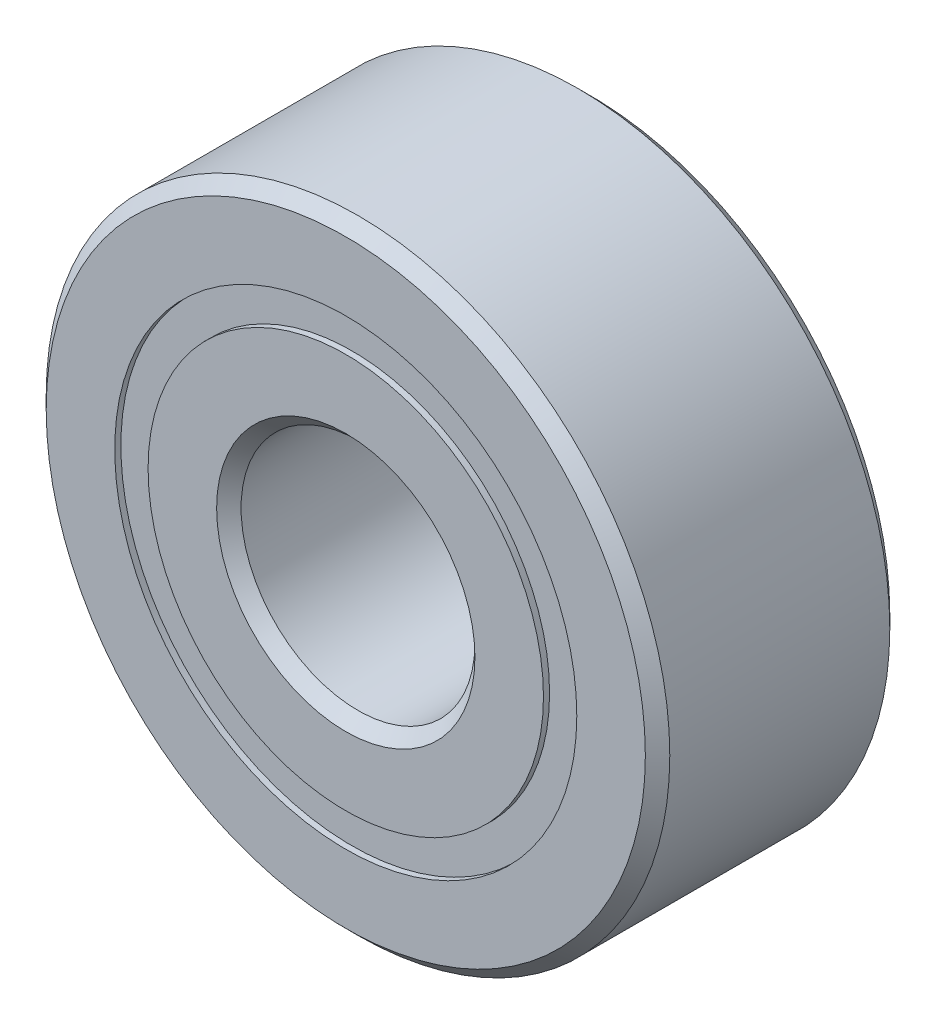
SolidWorks part; units mm, degrees
ref_plane "Front Plane" through (0, 0, 0) normal (0, 0, 1) x (1, 0, 0)
ref_plane "Top Plane" through (0, 0, 0) normal (0, 1, 0) x (1, 0, 0)
ref_plane "Right Plane" through (0, 0, 0) normal (1, 0, 0) x (0, 0, -1)
sketch "Sketch1" plane through (0, 0, 0) normal (1, 0, 0) x (0, 0, -1)
  line L0 (-2.4892, 0) -> (2.4892, 0) construction
  line L1 (0, 6.35) -> (0, -6.35) construction
  line L2 (2.2403, 6.35) -> (-2.2403, 6.35)
  line L3 (-2.2403, 6.35) -> (-2.4892, 6.1011)
  line L4 (-2.4892, 6.1011) -> (-2.4892, 4.705)
  line L5 (-2.4892, 4.705) -> (-1.1063, 4.705)
  line L6 (2.4892, 4.705) -> (1.1063, 4.705)
  line L7 (2.4892, 6.1011) -> (2.4892, 4.705)
  line L8 (2.2403, 6.35) -> (2.4892, 6.1011)
  line L9 (0, 6.35) -> (0, 4.3656) construction
  line L10 (0, 4.3656) -> (0, 2.3813) construction
  arc A0 (-1.1063, 4.705) -> (1.1063, 4.705) centre (0, 4.3656) cw
  point P14 (0, 2.3813)
  dimension "Width" = 4.9784
  dimension "OD" = 12.7
  dimension "D1" = 45
  dimension "D2" = 0.2489
  dimension "D3" = 2.2126
  dimension "D4" = 0.3394
revolve "Revolve1" add sketch "Sketch1" angle 360 about L0
sketch "Sketch3" plane through (0, 0, 0) normal (1, 0, 0) x (0, 0, -1)
  line L0 (-1.1063, 4.0262) -> (-2.4892, 4.0262)
  line L1 (-2.4892, 6.1011) -> (-2.4892, 4.705) construction
  line L2 (-2.2403, 6.35) -> (-2.4892, 6.1011) construction
  line L3 (-2.4892, 4.0262) -> (-2.4892, 2.6302)
  line L5 (-2.4892, 2.6302) -> (-2.2403, 2.3813)
  line L6 (-2.2403, 2.3813) -> (2.2403, 2.3812)
  line L7 (2.2403, 6.35) -> (2.2403, -6.35) construction
  line L8 (2.2403, 2.3812) -> (2.4892, 2.6302)
  line L9 (2.4892, -6.1011) -> (2.4892, 6.1011) construction
  line L10 (2.4892, 2.6302) -> (2.4892, 4.0262)
  line L11 (2.4892, 4.0262) -> (1.1063, 4.0262)
  line L12 (0, 6.35) -> (0, -6.35) construction
  line L13 (2.2403, 6.35) -> (2.4892, 6.1011) construction
  arc A1 (1.1063, 4.0262) -> (-1.1063, 4.0262) centre (0, 4.3656) cw
  arc A2 (1.1063, 4.705) -> (-1.1063, 4.705) centre (0, 4.3656) ccw construction
revolve "Revolve3" add sketch "Sketch3" angle 360 about L0
sketch "Sketch4" plane through (0, 0, 0) normal (1, 0, 0) x (0, 0, -1)
  line L0 (-1.1572, 4.3656) -> (1.1572, 4.3656)
  arc A2 (-1.1572, 4.3656) -> (1.1572, 4.3656) centre (0, 4.3656) cw
  arc A3 (1.1063, 4.705) -> (-1.1063, 4.705) centre (0, 4.3656) ccw construction
revolve "Revolve4" add sketch "Sketch4" angle 360 about L0
ref_axis "Axis1" through (0, 0, -2.4892) along (0, 0, 1)
pattern_circular "CirPattern1" count 10 every 36 about axis through (0, 0, -2.4892) along (0, 0, 1) of bodies 104
sketch "Sketch5" plane through (0, 0, 0) normal (1, 0, 0) x (0, 0, -1)
  line L0 (-2.4892, 4.705) -> (-1.1063, 4.705) construction
  line L1 (-2.3647, 4.705) -> (-1.1572, 4.705)
  line L2 (-2.3647, 4.705) -> (-2.3647, 4.0262)
  line L3 (-2.3647, 4.0262) -> (-1.1572, 4.0262)
  line L4 (-1.1572, 4.705) -> (-1.1572, 4.0262)
  line L5 (-1.1063, 4.0262) -> (-2.4892, 4.0262) construction
  line L6 (2.4892, 4.705) -> (1.1063, 4.705) construction
  line L7 (2.3647, 4.705) -> (1.1572, 4.705)
  line L8 (2.3647, 4.705) -> (2.3647, 4.0262)
  line L9 (2.3647, 4.0262) -> (1.1572, 4.0262)
  line L10 (1.1572, 4.705) -> (1.1572, 4.0262)
  line L11 (2.4892, 4.0262) -> (1.1063, 4.0262) construction
  line L12 (-2.2403, 6.35) -> (-2.4892, 6.1011) construction
  point P18 (-2.3647, 6.2255)
revolve "Revolve5" add sketch "Sketch5" angle 360 about L0
equation "\"D2@Sketch1\" = \"Width@Sketch1\"*.05"
equation "\"D3@Sketch1\" = \"Width@Sketch1\"/2.25"
equation "\"D4@Sketch1\" = (((\"OD@Sketch1\"-\"Width@Sketch1\")/2)/3.25)/3.5"
equation "\"D2@CirPattern1\" = 360/\"Balls@CirPattern1\""
